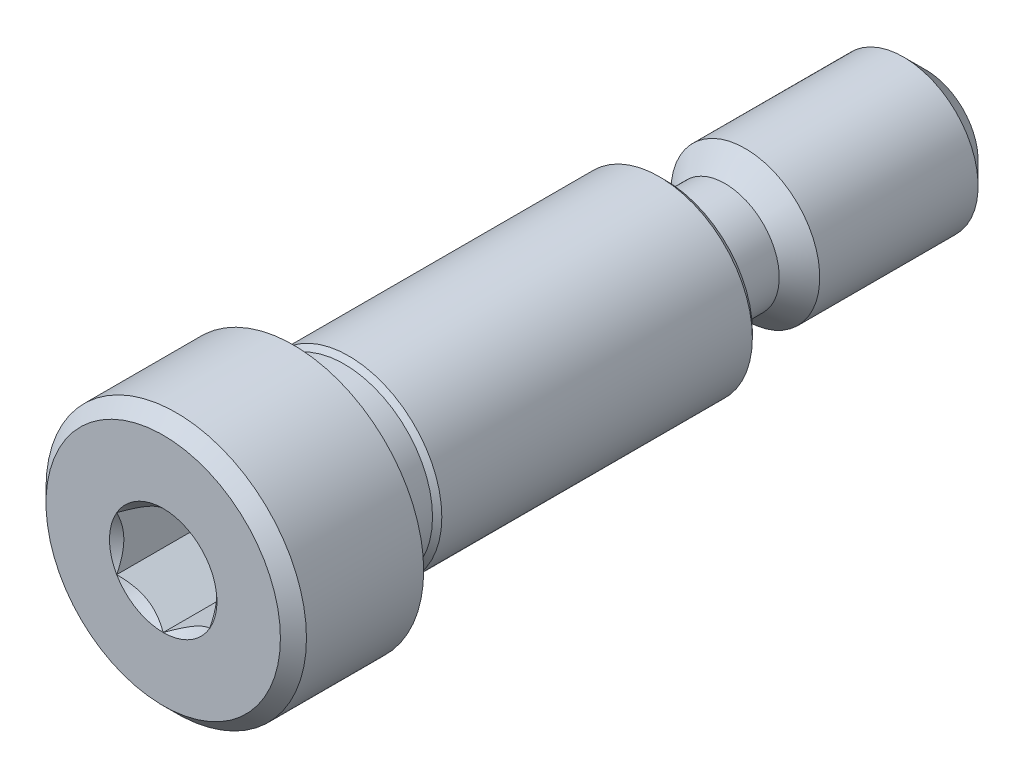
SolidWorks part; units mm, degrees
ref_plane "Front Plane" through (0, 0, 0) normal (0, 0, 1) x (1, 0, 0)
ref_plane "Top Plane" through (0, 0, 0) normal (0, 1, 0) x (1, 0, 0)
ref_plane "Right Plane" through (0, 0, 0) normal (1, 0, 0) x (0, 0, -1)
sketch "Sketch2" plane through (0, 0, 0) normal (1, 0, 0) x (0, 0, -1)
  line L0 (-16.2719, 0) -> (16.2719, 0) construction
  line L1 (-16.2719, 0) -> (-16.2719, 5.5562)
  line L2 (-16.2719, 5.5562) -> (-10.7156, 5.5562)
  line L3 (-10.7156, 5.5562) -> (-10.7156, 3.9688)
  line L4 (-10.7156, 3.9688) -> (5.1594, 3.9688)
  line L5 (5.1594, 3.175) -> (16.2719, 3.175)
  line L6 (16.2719, 3.175) -> (16.2719, 0)
  line L7 (16.1925, 3.3125) -> (16.8275, 2.2126) construction
  line L8 (16.8275, 2.2126) -> (17.4625, 3.3125) construction
  line L9 (17.4625, 3.3125) -> (16.1925, 3.3125) construction
  line L10 (16.2719, 3.175) -> (17.3831, 3.175) construction
  line L11 (16.8275, 3.3125) -> (16.8275, 3.175) construction
  line L12 (16.8275, 3.175) -> (16.8275, 2.3501) construction
  line L13 (16.8275, 2.3501) -> (16.8275, 2.2126) construction
  line L14 (16.7481, 2.3501) -> (16.9069, 2.3501)
  line L15 (16.2322, 3.2437) -> (17.4228, 3.2437)
  line L16 (16.9069, 2.3501) -> (17.4228, 3.2437)
  line L17 (16.7481, 2.3501) -> (16.2322, 3.2437)
  line L18 (16.2719, 0) -> (16.2719, -3.175) construction
  line L19 (5.1594, -3.9688) -> (5.1594, 0) construction
  line L20 (5.1594, 0) -> (5.1594, 3.9688) construction
  line L21 (-16.2719, 0) -> (-16.2719, -5.5562) construction
  point P11 (-8.3534, 3.9688)
  point P12 (13.0969, -3.175)
  point P22 (16.8275, 3.2437)
  point P23 (4.6037, 0)
  point P25 (-4.6037, 0)
  point P26 (-10.7156, -5.5562)
  point P29 (5.1594, -3.9688)
  dimension "Head Height" = 5.5562
  dimension "Shoulder Diameter" = 7.9375
  dimension "Screw Size Decimal Equivalent" = 6.35
  dimension "Thread Length" = 11.1125
  dimension "Head Diameter" = 11.1125
  dimension "Undercut Length" = 2.3622
  dimension "Pitch" = 1.27
  dimension "D2" = 0.1588
  dimension "D1" = 3.175
  dimension "D3" = 11.6681
  dimension "D4" = 11.6681
  dimension "Shoulder Length" = 15.875
sketch "Sketch3" plane through (0, 0, 0) normal (0, 0, 1) x (1, 0, 0)
  line L1 (0, 2.2914) -> (-1.9844, 1.1457)
  line L2 (-1.9844, 1.1457) -> (-1.9844, -1.1457)
  line L3 (-1.9844, -1.1457) -> (0, -2.2914)
  line L4 (0, -2.2914) -> (1.9844, -1.1457)
  line L5 (1.9844, -1.1457) -> (1.9844, 1.1457)
  line L6 (1.9844, 1.1457) -> (0, 2.2914)
  circle A0 centre (0, 0) radius 1.9844 construction
  dimension "Drive Size" = 3.9688
sketch "Sketch4" plane through (0, 0, 0) normal (1, 0, 0) x (0, 0, -1)
  line L0 (-10.7156, 5.5562) -> (-15.7162, 5.5562)
  line L1 (-15.7162, 5.5562) -> (-16.2719, 5.0006)
  line L2 (-10.7156, 5.5562) -> (-10.7156, 3.9688)
  line L3 (-10.7156, 3.9688) -> (-10.5172, 3.7703)
  line L4 (-10.5172, 3.7703) -> (-8.5519, 3.7703)
  line L5 (-8.5519, 3.7703) -> (-8.3534, 3.9688)
  line L6 (-10.7156, 3.9688) -> (5.1594, 3.9688) construction
  line L7 (-16.2719, 0) -> (16.2719, 0) construction
  line L8 (-8.3534, 3.9688) -> (4.8948, 3.9688)
  line L9 (4.8948, 3.9688) -> (5.1594, 3.7042)
  line L10 (5.1594, 3.7042) -> (5.1594, 0)
  line L11 (5.1594, 3.9688) -> (5.1594, 3.7042) construction
  line L12 (5.1594, 3.7042) -> (5.1594, 3.4396) construction
  line L13 (5.1594, 3.4396) -> (5.1594, 3.175) construction
  line L14 (-16.2719, 5.0006) -> (-16.2719, 0)
  line L15 (-16.2719, 5.5562) -> (-10.7156, 5.5562) construction
  line L16 (-16.2719, 0) -> (5.1594, 0)
  dimension "D1" = 45
  dimension "D2" = 7.5406
  dimension "D3" = 45
  dimension "D4" = 45
  dimension "D5" = 10.0012
revolve "Revolve1" add sketch "Sketch4" angle 360 about L16
sketch "Sketch5" plane through (0, 0, 16.2719) normal (0, 0, 1) x (1, 0, 0)
  line L0 (1.9844, 1.1457) -> (0, 2.2914) construction
  line L1 (1.9844, -1.1457) -> (1.9844, 1.1457) construction
  line L2 (0, -2.2914) -> (1.9844, -1.1457) construction
  line L3 (-1.9844, -1.1457) -> (0, -2.2914) construction
  line L4 (-1.9844, 1.1457) -> (-1.9844, -1.1457) construction
  line L5 (0, 2.2914) -> (-1.9844, 1.1457) construction
  line L6 (1.9844, 1.1457) -> (0, 2.2914)
  line L7 (1.9844, -1.1457) -> (1.9844, 1.1457)
  line L8 (0, -2.2914) -> (1.9844, -1.1457)
  line L9 (-1.9844, -1.1457) -> (0, -2.2914)
  line L10 (-1.9844, 1.1457) -> (-1.9844, -1.1457)
  line L11 (0, 2.2914) -> (-1.9844, 1.1457)
extrude "Cut-Extrude1" cut sketch "Sketch5" against normal blind 4.1672
sketch "Sketch6" plane through (0, 0, 16.2719) normal (0, 0, 1) x (1, 0, 0)
  circle A0 centre (0, 0) radius 2.2914
extrude "Cut-Extrude4" cut sketch "Sketch6" against normal blind 4.1672 draft 45
sketch "Sketch7" plane through (0, 0, 0) normal (1, 0, 0) x (0, 0, -1)
  line L0 (5.1594, 3.175) -> (15.3194, 3.175)
  line L1 (5.1594, 3.175) -> (16.2719, 3.175) construction
  line L2 (15.3194, 3.175) -> (16.2719, 2.2225)
  line L3 (16.2719, 3.175) -> (16.2719, 0) construction
  line L4 (16.2719, 2.2225) -> (16.2719, 0)
  line L5 (16.2719, 0) -> (5.1594, 0)
  line L6 (5.1594, -3.7042) -> (5.1594, 3.7042) construction
  line L7 (5.1594, 0) -> (5.1594, 3.175)
  dimension "D1" = 45
  dimension "D2" = 0.9525
revolve "Revolve2" add sketch "Sketch7" angle 360 about L5
sketch "Sketch10" plane through (0, 0, 0) normal (1, 0, 0) x (0, 0, -1)
  line L0 (6.023, 2.3114) -> (7.6994, 2.3114)
  line L1 (7.6994, 2.3114) -> (9.3567, 3.9688)
  line L2 (9.3567, 3.9688) -> (5.1594, 3.9688)
  line L3 (5.1594, 3.9688) -> (5.1594, 3.175)
  line L4 (5.1594, -3.7042) -> (5.1594, 3.7042) construction
  line L5 (16.2719, 0) -> (5.1594, 0) construction
  line L6 (-16.2719, 0) -> (16.2719, 0) construction
  arc A0 (5.1594, 3.175) -> (6.023, 2.3114) centre (6.023, 3.175) ccw
  dimension "Flat OD" = 4.6228
  dimension "Flat" = 2.54
  dimension "D3" = 45
revolve "Cut-Revolve1" cut sketch "Sketch10" angle 360 about L5
sketch "Sketch8" [suppressed] plane through (0, 0, -16.2719) normal (0, 0, -1) x (-1, 0, 0)
  circle A0 centre (0, 0) radius 3.175 construction
  circle A1 centre (0, 0) radius 3.175
curve "Helix/Spiral1" [suppressed] pitch 1.27 height 12.3825 turns 9.75
sketch "Sketch9" [suppressed] plane through (0, 0, 0) normal (1, 0, 0) x (0, 0, -1)
  line L0 (16.7481, 2.3501) -> (16.9069, 2.3501) construction
  line L1 (16.9069, 2.3501) -> (17.4228, 3.2437) construction
  line L2 (16.2322, 3.2437) -> (17.4228, 3.2437) construction
  line L3 (16.7481, 2.3501) -> (16.2322, 3.2437) construction
  line L4 (16.7481, 2.3501) -> (16.9069, 2.3501)
  line L5 (16.9069, 2.3501) -> (17.4228, 3.2437)
  line L6 (16.2322, 3.2437) -> (17.4228, 3.2437)
  line L7 (16.7481, 2.3501) -> (16.2322, 3.2437)
ref_plane "Plane1" [suppressed] through (0, 0, -7.6994) normal (0, 0, 1) x (1, 0, 0)
split "Split1" [suppressed] bodies to split 138
sweep "Cut-Sweep1" [suppressed] cut profiles "Sketch9" path "Helix/Spiral1"
combine bodies "Combine1" [suppressed] operation type add bodies to combine 141 139
sketch "Sketch11" [suppressed] plane through (0, 0, 16.2719) normal (0, 0, 1) x (1, 0, 0)
  line L0 (-0.0802, 5.5562) -> (0.0802, 5.5562)
  line L1 (0.0802, 5.5562) -> (0, 5.4173)
  line L2 (0, 0) -> (0, 5.5562) construction
  line L3 (0, 5.4173) -> (-0.0802, 5.5562)
  line L4 (0, 0) -> (5.5562, 0) construction
  circle A0 centre (0, 0) radius 5.5562 construction
  point P6 (0, 5.5562)
  dimension "D1" = 10.8347
  dimension "D2" = 60
  dimension "D3" = 0.1604
sketch "Sketch12" [suppressed] plane through (0, 0, 0) normal (1, 0, 0) x (0, 0, -1)
  line L0 (-16.2719, 5.4173) -> (-12.44, 5.4173)
  line L1 (-11.9658, 5.8916) -> (-11.9658, 5.5562) construction
  line L2 (-16.2719, 5.5562) -> (-10.7156, 5.5562) construction
  arc A0 (-12.44, 5.4173) -> (-11.9658, 5.8916) centre (-12.44, 5.8916) ccw
  point P11 (-12.1047, 5.5563)
  dimension "D1" = 1.3891
sweep "Cut-Sweep2" [suppressed] cut profiles "Sketch11" path "Sketch12"
pattern_circular "CirPattern1" [suppressed] count 76 over 360 about axis through (0, 0, 16.2719) along (0, 0, -1) of bodies 143
sketch "Sketch13" plane through (0, 0, 12.1047) normal (0, 0, 1) x (1, 0, 0)
  circle A0 centre (0, 0) radius 2.2914
equation "\"D2@Sketch2\" = \"Pitch@Sketch2\" / 8"
equation "\"D1@Sketch2\"=\"Pitch@Sketch2\"*2.5"
equation "\"D2@Sketch4\"=\"Shoulder Diameter@Sketch2\"*0.95"
equation "\"D5@Sketch4\"=\"Head Diameter@Sketch2\"*0.9"
equation "\"D1@Cut-Extrude1\"=\"Head Height@Sketch2\"*0.75"
equation "\"D1@Cut-Extrude4\"=\"D1@Cut-Extrude1\""
equation "\"D2@Sketch7\"=\"pitch@sketch2\"*0.75"
equation "\"D3@Helix/Spiral1\"=\"Thread Length@Sketch2\"+\"Pitch@Sketch2\""
equation "\"D4@Helix/Spiral1\"=\"Pitch@Sketch2\""
equation "\"D1@Sketch11\"=\"Head Diameter@Sketch2\"*0.975"
equation "\"D1@Sketch12\"=\"Head Height@Sketch2\"*0.25"
equation "\"D1@CirPattern1\"=\"Head Diameter@Sketch2\" * 3.14 / \"D3@Sketch11\" * 0.35"
equation "\"D3@Sketch2\"=\"Thread Length@Sketch2\"*1.05"
equation "\"D4@Sketch2\"=\"D3@Sketch2\""
